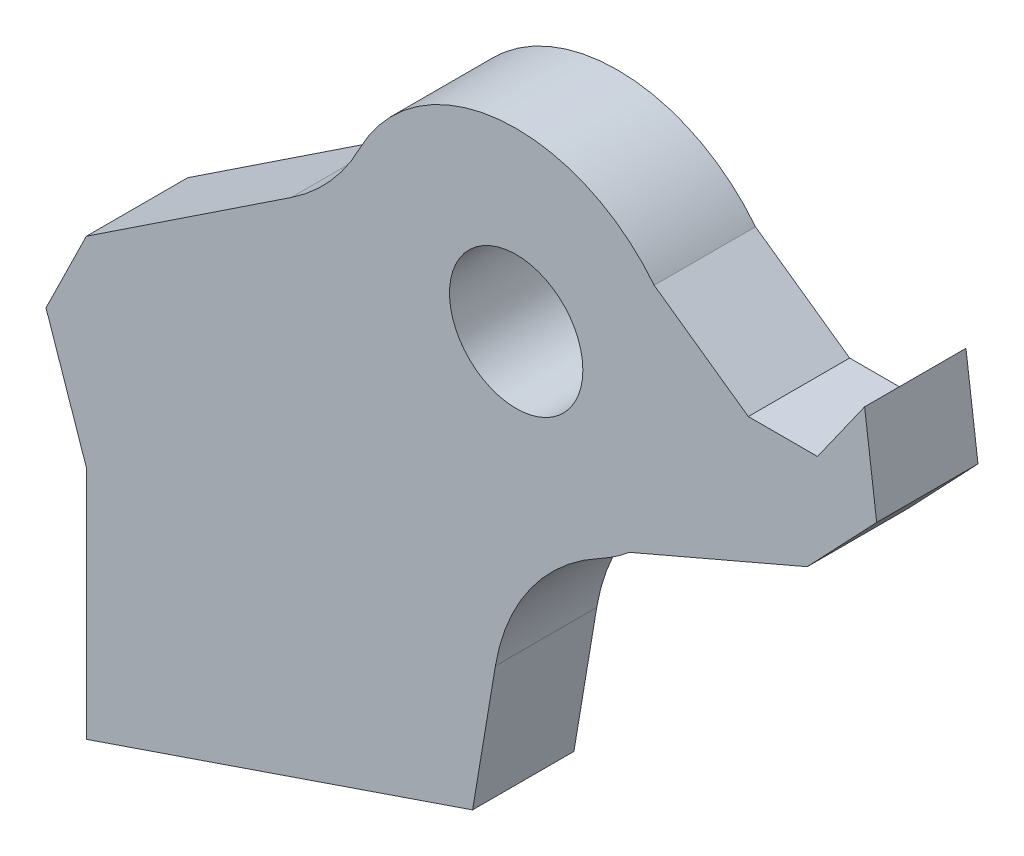
SolidWorks part; units mm, degrees
ref_plane "Front Plane" through (0, 0, 0) normal (0, 0, 1) x (1, 0, 0)
ref_plane "Top Plane" through (0, 0, 0) normal (0, 1, 0) x (1, 0, 0)
ref_plane "Right Plane" through (0, 0, 0) normal (1, 0, 0) x (0, 0, -1)
sketch "Sketch1" plane through (0, 0, 0) normal (0, 0, 1) x (1, 0, 0)
  line L0 (596.3019, 140.0618) -> (593.7757, 134.9133)
  line L1 (593.7757, 134.9133) -> (596.3019, 127.5195)
  line L2 (596.3019, 127.5195) -> (596.3019, 112.7612)
  line L3 (596.3019, 112.7612) -> (620.507, 121.0314)
  line L4 (620.507, 121.0314) -> (621.9354, 129.559)
  line L6 (631.8868, 155.1927) -> (637.7848, 151.019)
  line L7 (637.7848, 151.019) -> (642.1201, 151.019)
  line L8 (642.1201, 151.019) -> (645.0736, 155.1927)
  line L9 (645.0736, 155.1927) -> (645.8281, 149.2934)
  line L10 (645.8281, 149.2934) -> (641.4752, 144.7139)
  line L11 (641.4752, 144.7139) -> (630.3276, 139.9208)
  line L12 (596.3019, 140.0618) -> (609.1463, 148.5881)
  circle A0 centre (623.2385, 148.3601) radius 4.1787
  arc A1 (628.4527, 138.6499) -> (630.3276, 139.9208) centre (623.2385, 148.3601) ccw
  arc A2 (621.9354, 129.559) -> (628.4527, 138.6499) centre (634.4609, 127.461) cw
  arc A3 (613.4275, 153.3822) -> (609.1463, 148.5881) centre (602.1225, 159.1691) cw
  arc A4 (631.8868, 155.1927) -> (613.4275, 153.3822) centre (623.2385, 148.3601) ccw
  point P18 (623.2385, 137.3385)
  dimension "D1" = 12.7
extrude "Boss-Extrude1" add sketch "Sketch1" along normal blind 3.175 and the other way blind 3.175 contours A0 | L2 L3 L4 A2 A1 L11 L10 L9 L8 L7 L6 A4 A3 L12 L0 L1 region at (623.2385, 148.3601, 0)
